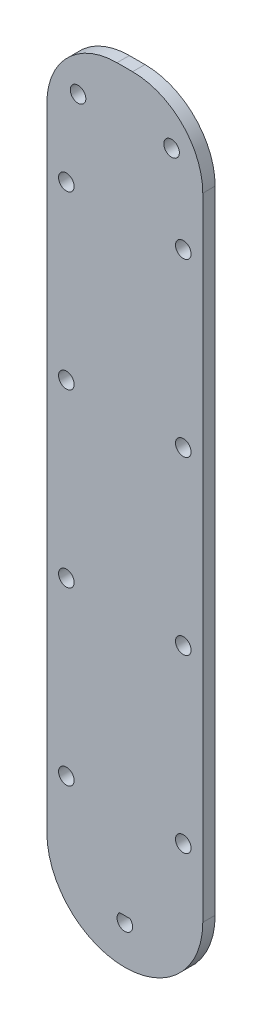
SolidWorks part; units mm, degrees
material "Acrylic (Medium-high impact)"
ref_plane "Front" through (0, 0, 0) normal (0, 0, 1) x (1, 0, 0)
ref_plane "Top" through (0, 0, 0) normal (0, 1, 0) x (1, 0, 0)
ref_plane "Right" through (0, 0, 0) normal (1, 0, 0) x (0, 0, -1)
sketch "Sketch2" plane through (0, 0, 0) normal (0, 0, 1) x (1, 0, 0)
  line L1 (-20, -100) -> (20, -100)
  line L2 (-20, -100) -> (-20, 100)
  line L3 (-20, 100) -> (20, 100)
  line L4 (20, -100) -> (20, 100)
  line L5 (-20, -100) -> (20, 100) construction
  line L6 (-20, 100) -> (20, -100) construction
  point P1 (0, 0)
  dimension "D1" = 200
  dimension "D2" = 40
extrude "Boss-Extrude1" add sketch "Sketch2" along normal blind 3.175
sketch "Sketch3" plane through (0, 0, 0) normal (0, 0, -1) x (-1, 0, 0)
  line L0 (20, -100) -> (-20, -100) construction
  line L1 (1.325, -88.5019) -> (-1.325, -88.5019)
  arc A0 (-1.325, -88.5019) -> (1.325, -88.5019) centre (0, -90) ccw
  dimension "D1" = 4
  dimension "D2" = 10
  dimension "D3" = 2.65
extrude "Cut-Extrude1" cut sketch "Sketch3" against normal blind 10
fillet "Fillet1" radius 20 2 edges at (20, -100, 1.5875) (-20, -100, 1.5875)
fillet "Fillet2" radius 18 2 edges at (20, 100, 1.5875) (-20, 100, 1.5875)
sketch "Sketch6" plane through (0, 0, 3.175) normal (0, 0, 1) x (1, 0, 0)
  line L0 (0, -113.8198) -> (0, 113.8198) construction
  line L1 (15, 67) -> (15, 23) construction
  line L2 (15, 23) -> (15, -21) construction
  line L3 (15, -21) -> (15, -65) construction
  line L4 (20, -80) -> (20, 82) construction
  line L5 (-15, -21) -> (-15, -65) construction
  line L6 (-15, 23) -> (-15, -21) construction
  line L7 (-15, 67) -> (-15, 23) construction
  circle A0 centre (15, 67) radius 2
  circle A1 centre (15, -21) radius 2
  circle A2 centre (15, 23) radius 2
  circle A3 centre (15, -65) radius 2
  circle A4 centre (-15, -65) radius 2
  circle A5 centre (-15, 23) radius 2
  circle A6 centre (-15, -21) radius 2
  circle A7 centre (-15, 67) radius 2
  point P11 (0, 0)
  dimension "D1" = 4
  dimension "D2" = 15
  dimension "5" = 5
  dimension "D3" = 15
extrude "Cut-Extrude4" cut sketch "Sketch6" against normal through all
sketch "Sketch7" plane through (0, 0, 3.175) normal (0, 0, 1) x (1, 0, 0)
  line L0 (-30.4029, 88) -> (30.4029, 88) construction
  circle A0 centre (-12, 88) radius 2
  circle A1 centre (12, 88) radius 2
  point P4 (0, 88)
  dimension "D1" = 4
  dimension "D2" = 4
  dimension "D3" = 12
  dimension "D4" = 12
extrude "Cut-Extrude5" cut sketch "Sketch7" against normal through all
